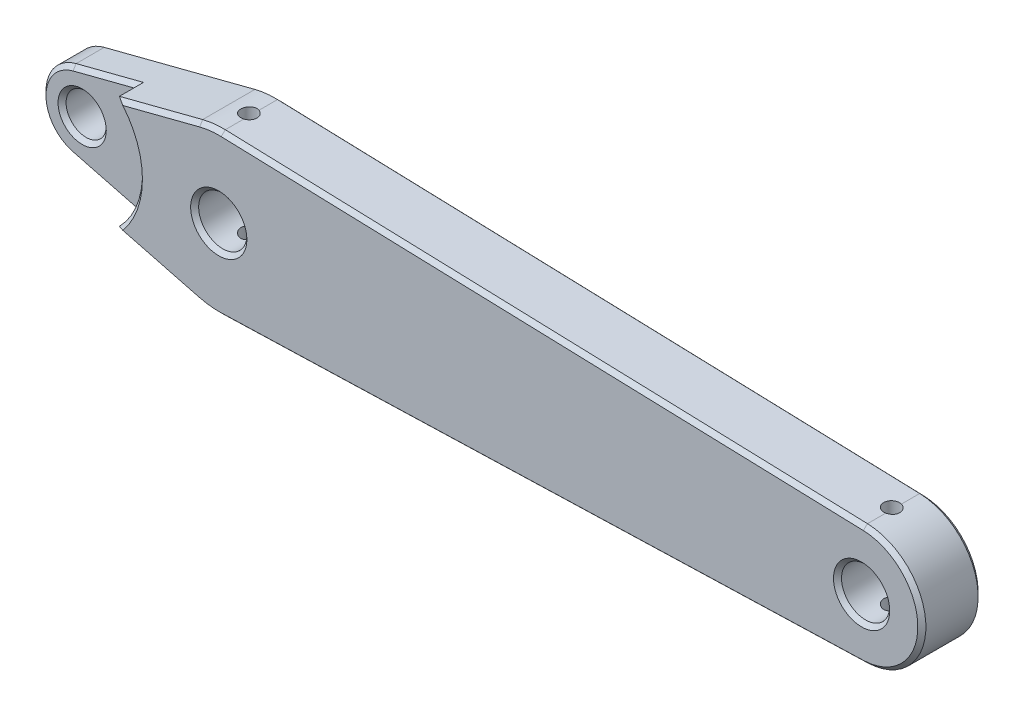
SolidWorks part; units mm, degrees
material "6061-T6 (GB)"
ref_plane "前视" through (0, 0, 0) normal (0, 0, 1) x (1, 0, 0)
ref_plane "上视" through (0, 0, 0) normal (0, 1, 0) x (1, 0, 0)
ref_plane "右视" through (0, 0, 0) normal (1, 0, 0) x (0, 0, -1)
sketch "草图1" plane through (0, 0, 0) normal (0, 0, 1) x (1, 0, 0)
  line L0 (-20, 0) -> (80, 0) construction
  line L1 (-21.25, 4.8412) -> (-2.5, 9.6825)
  line L2 (0.3125, 9.9951) -> (80.2344, 7.4963)
  line L3 (0.3125, -9.9951) -> (80.2344, -7.4963)
  line L4 (-21.25, -4.8412) -> (-2.5, -9.6825)
  circle A0 centre (-20, 0) radius 2.5
  circle A1 centre (0, 0) radius 3
  circle A2 centre (80, 0) radius 3
  arc A3 (-21.25, 4.8412) -> (-21.25, -4.8412) centre (-20, 0) ccw
  arc A4 (-2.5, -9.6825) -> (0.3125, -9.9951) centre (0, 0) ccw
  arc A5 (80.2344, -7.4963) -> (80.2344, 7.4963) centre (80, 0) ccw
  arc A6 (0.3125, 9.9951) -> (-2.5, 9.6825) centre (0, 0) ccw
  point P13 (84.5614, 12.1993)
  dimension "D1" = 80
  dimension "D2" = 20
  dimension "D3" = 6
  dimension "D4" = 6
  dimension "D5" = 5
  dimension "D6" = 10
  dimension "D7" = 20
  dimension "D8" = 15
extrude "凸台-拉伸1" add sketch "草图1" along normal mid plane 7.5
sketch "草图2" plane through (0, 0, 0) normal (0, 1, 0) x (1, 0, 0)
  line L0 (-35.8355, 0) -> (100.0094, 0) construction
  line L1 (80, 0) -> (80, 5.3314) construction
  line L2 (77, 3.75) -> (77, -3.75) construction
  line L3 (83, -3.75) -> (83, 3.75) construction
  circle A0 centre (0, 0) radius 1
  circle A1 centre (80, 0) radius 1
  dimension "D1" = 2
extrude "切除-拉伸1" cut sketch "草图2" against normal mid plane 40
sketch "草图3" plane through (0, 0, 3.75) normal (0, 0, 1) x (1, 0, 0)
  circle A0 centre (-20, 0) radius 10
  dimension "D1" = 20
extrude "切除-拉伸2" cut sketch "草图3" against normal blind 3
chamfer "倒角1" distance 0.5 angle 45 25 edges at (83, 0, -3.75) (3, 0, -3.75) (-17.5, 0, -3.75) (-11.875, 7.2618, -3.75) (-25, 0, -3.75) (-11.875, -7.2618, -3.75) (-1.1049, -9.9388, -3.75) (40.2734, -8.7457, -3.75) (87.5, 0, -3.75) (40.2734, 8.7457, -3.75) (-1.1049, 9.9388, -3.75) (83, 0, 3.75) (3, 0, 3.75) (-7.6824, 8.3444, 3.75) (-1.1049, 9.9388, 3.75) (40.2734, 8.7457, 3.75) (87.5, 0, 3.75) (40.2734, -8.7457, 3.75) (-1.1049, -9.9388, 3.75) (-7.6824, -8.3444, 3.75) (-10, 0, 3.75) (-17.0574, 5.9238, 0.75) (-25, 0, 0.75) (-17.0574, -5.9238, 0.75) (-17.5, 0, 0.75)
